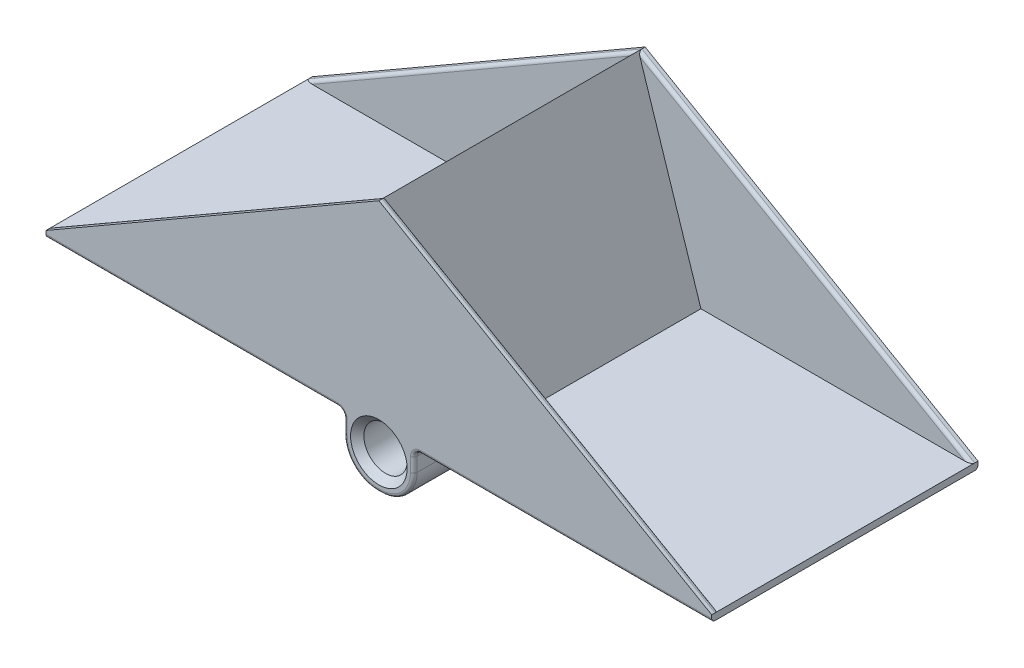
SolidWorks part; units mm, degrees
material "ABS"
ref_plane "Alzado" through (0, 0, 0) normal (0, 0, 1) x (1, 0, 0)
ref_plane "Planta" through (0, 0, 0) normal (0, 1, 0) x (1, 0, 0)
ref_plane "Vista lateral" through (0, 0, 0) normal (1, 0, 0) x (0, 0, -1)
ref_plane "Plano2" through (0, 0, 20) normal (0, 0, 1) x (1, 0, 0)
sketch "Croquis1" plane through (0, 0, 20) normal (0, 0, 1) x (1, 0, 0)
  line L0 (0, 43.1974) -> (0, -36.2286) construction
  line L1 (-50, 0) -> (50, 0)
  line L2 (0, 0) -> (0, 28.8675)
  line L3 (0, 28.8675) -> (-50, 0)
  line L4 (0, 28.8675) -> (50, 0)
  dimension "D1" = 100
  dimension "D2" = 28.8675
extrude "Saliente-Extruir1" add sketch "Croquis1" against normal blind 1 contours L3 L1 L4
mirror "Simetría4" about plane through (0, 0, 0) normal (0, 0, 1) of bodies 121
sketch "Croquis3" plane through (0, 0, 0) normal (0, 1, 0) x (1, 0, 0)
  line L1 (50, -20) -> (-50, -20)
  line L2 (50, -20) -> (50, 20)
  line L3 (50, 20) -> (-50, 20)
  line L4 (-50, -20) -> (-50, 20)
extrude "Saliente-Extruir2" add sketch "Croquis3" against normal blind 1
sketch "Croquis5" plane through (0, 0, 0) normal (0, 0, 1) x (1, 0, 0)
  line L0 (-5.25, -1) -> (-5.25, -9.1)
  line L1 (-16.1852, 0) -> (16.1852, 0) construction
  line L2 (-11.187, -1) -> (16.4285, -1) construction
  line L3 (-50, -1) -> (50, -1) construction
  line L4 (-5.25, -1) -> (5.25, -1)
  line L5 (-5.25, -9.1) -> (5.25, -9.1)
  line L6 (5.25, -9.1) -> (5.25, -1)
  line L7 (0, 0) -> (0, -17.436) construction
  circle A4 centre (0, -3.85) radius 3.25 construction
  dimension "D2" = 6.5
  dimension "D3" = 1
  dimension "D4" = 5.25
  dimension "D5" = 10.5
  dimension "D1" = 8.1
extrude "Saliente-Extruir3" add sketch "Croquis5" along normal mid plane 40
sketch "Croquis6" plane through (0, 0, 0) normal (0, 0, 1) x (1, 0, 0)
  line L0 (0, 28.8675) -> (0, -22.6843) construction
  line L1 (0, 28.8675) -> (9.3796, 0)
  line L2 (9.3796, 0) -> (-9.3796, 0)
  line L3 (-9.3796, 0) -> (0, 28.8675)
  dimension "D1" = 36
extrude "Saliente-Extruir4" add sketch "Croquis6" along normal mid plane 40
sketch "Croquis7" plane through (0, 0, -19) normal (0, 0, 1) x (1, 0, 0)
  line L0 (0, 0) -> (0, -12.2969) construction
  line L2 (-5.25, -9.1) -> (5.25, -9.1) construction
  circle A0 centre (0, -3.85) radius 3.25
  dimension "D1" = 6.5
  dimension "D2" = 5.25
extrude "Cortar-Extruir1" cut sketch "Croquis7" along normal mid plane 200 contours A0
fillet "Redondeo2" radius 5 2 edges at (5.25, -9.1, 0) (-5.25, -9.1, 0)
chamfer "Chaflán2" distance 1 angle 45 2 edges at (-3.25, -3.85, 20) (-3.25, -3.85, -20)
fillet "Redondeo3" radius 1 2 edges at (5.25, -1, 0) (-5.25, -1, 0)
fillet "Redondeo4" radius 0.5 18 edges at (-28.125, -1, -20) (-5.25, -3.05, -20) (0, -9.1, -20) (5.25, -3.05, -20) (28.125, -1, 20) (5.25, -3.05, 20) (0, -9.1, 20) (-5.25, -3.05, 20) (28.125, -1, -20) (-28.125, -1, 20) (5.5429, -1.2929, -20) (-5.5429, -1.2929, 20) (-5.5429, -1.2929, -20) (-3.7855, -7.6355, -20) (3.7855, -7.6355, -20) (5.5429, -1.2929, 20) (3.7855, -7.6355, 20) (-3.7855, -7.6355, 20)
fillet "Redondeo5" radius 0.5 4 edges at (25, 14.4338, 19) (-25, 14.4338, 19) (25, 14.4338, -19) (-25, 14.4338, -19)
equation "\"B\"= 100"
equation "\"h\"= \"B\" / 2 * tan ( \"an\" )"
equation "\"an\"= 30"
equation "\"w\"= 6.5"
equation "\"z\"= 1"
equation "\"p\"= 40mm"
equation "\"r\"= 8.1"
equation "\"D1@Croquis1\"=\"B\""
equation "\"D2@Croquis1\"=\"h\""
equation "\"D1@Saliente-Extruir1\"=\"z\""
equation "\"d\"= ( \"p\" - \"z\" / 2 ) / 2"
equation "\"D1@Saliente-Extruir2\"=\"z\""
equation "\"teta\"= 18"
equation "\"D2@Croquis5\"=\"w\""
equation "\"D4@Croquis5\"=\"w\"/2+2"
equation "\"D5@Croquis5\"=\"w\"+4"
equation "\"D1@Croquis5\"=\"r\""
equation "\"D1@Saliente-Extruir3\"=\"p\""
equation "\"D1@Croquis6\"=2*\"teta\""
equation "\"D1@Saliente-Extruir4\"=\"p\""
equation "\"D1@Plano2\"=\"p\"/2"
